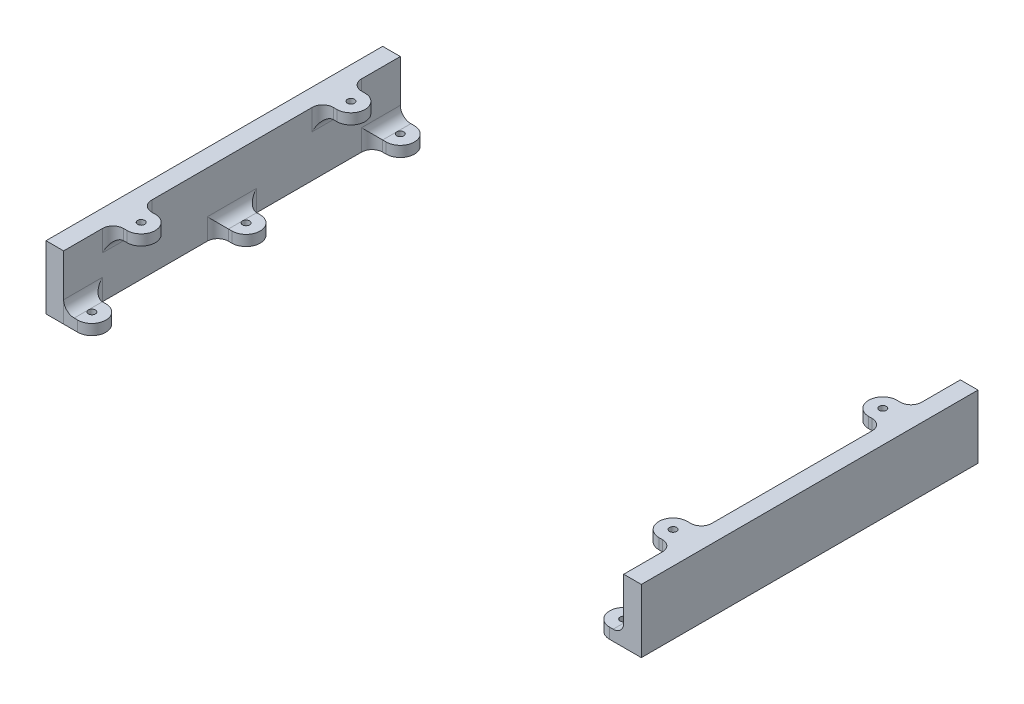
SolidWorks part; units mm, degrees
ref_plane "Front Plane" through (0, 0, 0) normal (0, 0, 1) x (1, 0, 0)
ref_plane "Top Plane" through (0, 0, 0) normal (0, 1, 0) x (1, 0, 0)
ref_plane "Right Plane" through (0, 0, 0) normal (1, 0, 0) x (0, 0, -1)
sketch "Sketch1" plane through (0, 20, 0) normal (0, 1, 0) x (1, 0, 0)
  line L11 (-48.875, 4.25) -> (-53.875, 4.25)
  line L12 (-53.875, 4.25) -> (-53.875, -91.25)
  line L13 (-53.875, -91.25) -> (-48.875, -91.25)
  line L14 (-48.875, -91.25) -> (-44.875, -91.25)
  line L15 (-44.875, -83.25) -> (-45.875, -83.25)
  line L16 (-48.875, -80.25) -> (-48.875, -50.5)
  line L17 (-45.875, -47.5) -> (-44.875, -47.5)
  line L18 (-44.875, -39.5) -> (-45.875, -39.5)
  line L19 (-48.875, -36.5) -> (-48.875, -6.75)
  line L20 (-45.875, -3.75) -> (-44.875, -3.75)
  line L21 (-44.875, 4.25) -> (-48.875, 4.25)
  line L22 (-48.875, 4.25) -> (-53.875, 4.25)
  line L23 (-53.875, 4.25) -> (-53.875, -91.25)
  line L24 (-53.875, -91.25) -> (-48.875, -91.25)
  line L25 (-48.875, -91.25) -> (-44.875, -91.25)
  line L26 (-44.875, -83.25) -> (-45.875, -83.25)
  line L27 (-48.875, -80.25) -> (-48.875, -50.5)
  line L28 (-45.875, -47.5) -> (-44.875, -47.5)
  line L29 (-44.875, -39.5) -> (-45.875, -39.5)
  line L30 (-48.875, -36.5) -> (-48.875, -6.75)
  line L31 (-45.875, -3.75) -> (-44.875, -3.75)
  line L32 (-44.875, 4.25) -> (-48.875, 4.25)
  line L33 (115, 4.25) -> (110, 4.25)
  line L34 (110, 4.25) -> (106, 4.25)
  line L35 (106, -3.75) -> (107, -3.75)
  line L36 (110, -6.75) -> (110, -36.5)
  line L37 (107, -39.5) -> (106, -39.5)
  line L38 (106, -47.5) -> (107, -47.5)
  line L39 (110, -50.5) -> (110, -80.25)
  line L40 (107, -83.25) -> (106, -83.25)
  line L41 (106, -91.25) -> (110, -91.25)
  line L42 (110, -91.25) -> (115, -91.25)
  line L43 (115, -91.25) -> (115, 4.25)
  line L44 (115, 4.25) -> (110, 4.25)
  line L45 (110, 4.25) -> (106, 4.25)
  line L46 (106, -3.75) -> (107, -3.75)
  line L47 (110, -6.75) -> (110, -36.5)
  line L48 (107, -39.5) -> (106, -39.5)
  line L49 (106, -47.5) -> (107, -47.5)
  line L50 (110, -50.5) -> (110, -80.25)
  line L51 (107, -83.25) -> (106, -83.25)
  line L52 (106, -91.25) -> (110, -91.25)
  line L53 (110, -91.25) -> (115, -91.25)
  line L54 (115, -91.25) -> (115, 4.25)
  circle A0 centre (106, -87.25) radius 1 construction
  circle A1 centre (106, -43.5) radius 1 construction
  circle A2 centre (106, -87.25) radius 1
  circle A3 centre (106, -43.5) radius 1
  circle A4 centre (-44.875, -87.25) radius 1 construction
  circle A5 centre (-44.875, -43.5) radius 1 construction
  circle A6 centre (-44.875, 0.25) radius 1 construction
  arc A7 (-44.875, -91.25) -> (-44.875, -83.25) centre (-44.875, -87.25) ccw
  arc A8 (-48.875, -80.25) -> (-45.875, -83.25) centre (-45.875, -80.25) ccw
  arc A9 (-45.875, -47.5) -> (-48.875, -50.5) centre (-45.875, -50.5) ccw
  arc A10 (-44.875, -47.5) -> (-44.875, -39.5) centre (-44.875, -43.5) ccw
  arc A11 (-48.875, -36.5) -> (-45.875, -39.5) centre (-45.875, -36.5) ccw
  arc A12 (-45.875, -3.75) -> (-48.875, -6.75) centre (-45.875, -6.75) ccw
  arc A13 (-44.875, -3.75) -> (-44.875, 4.25) centre (-44.875, 0.25) ccw
  arc A14 (-44.875, -91.25) -> (-44.875, -83.25) centre (-44.875, -87.25) ccw
  arc A15 (-48.875, -80.25) -> (-45.875, -83.25) centre (-45.875, -80.25) ccw
  arc A16 (-45.875, -47.5) -> (-48.875, -50.5) centre (-45.875, -50.5) ccw
  arc A17 (-44.875, -47.5) -> (-44.875, -39.5) centre (-44.875, -43.5) ccw
  arc A18 (-48.875, -36.5) -> (-45.875, -39.5) centre (-45.875, -36.5) ccw
  arc A19 (-45.875, -3.75) -> (-48.875, -6.75) centre (-45.875, -6.75) ccw
  arc A20 (-44.875, -3.75) -> (-44.875, 4.25) centre (-44.875, 0.25) ccw
  arc A21 (106, 4.25) -> (106, -3.75) centre (106, 0.25) ccw
  arc A22 (110, -6.75) -> (107, -3.75) centre (107, -6.75) ccw
  arc A23 (107, -39.5) -> (110, -36.5) centre (107, -36.5) ccw
  arc A24 (106, -39.5) -> (106, -47.5) centre (106, -43.5) ccw
  arc A25 (110, -50.5) -> (107, -47.5) centre (107, -50.5) ccw
  arc A26 (107, -83.25) -> (110, -80.25) centre (107, -80.25) ccw
  arc A27 (106, -83.25) -> (106, -91.25) centre (106, -87.25) ccw
  arc A28 (106, 4.25) -> (106, -3.75) centre (106, 0.25) ccw
  arc A29 (110, -6.75) -> (107, -3.75) centre (107, -6.75) ccw
  arc A30 (107, -39.5) -> (110, -36.5) centre (107, -36.5) ccw
  arc A31 (106, -39.5) -> (106, -47.5) centre (106, -43.5) ccw
  arc A32 (110, -50.5) -> (107, -47.5) centre (107, -50.5) ccw
  arc A33 (107, -83.25) -> (110, -80.25) centre (107, -80.25) ccw
  arc A34 (106, -83.25) -> (106, -91.25) centre (106, -87.25) ccw
  circle A35 centre (106, 0.25) radius 1 construction
  circle A36 centre (-44.875, -87.25) radius 1
  circle A37 centre (-44.875, -43.5) radius 1
  circle A38 centre (-44.875, 0.25) radius 1
  circle A39 centre (106, 0.25) radius 1
  dimension "D1" = 0
  dimension "D2" = 0
extrude "LEVEL 1 mating surface" add sketch "Sketch1" along normal blind 3
sketch "Sketch2" plane through (0, 23, 0) normal (0, 1, 0) x (1, 0, 0)
  line L1 (-53.875, 4.25) -> (-48.875, 4.25)
  line L2 (-53.875, 4.25) -> (-53.875, -91.25)
  line L3 (-53.875, -91.25) -> (-48.875, -91.25)
  line L4 (-48.875, 4.25) -> (-48.875, -91.25)
  line L5 (110, 4.25) -> (115, 4.25)
  line L6 (110, 4.25) -> (110, -91.25)
  line L7 (110, -91.25) -> (115, -91.25)
  line L8 (115, 4.25) -> (115, -91.25)
extrude "LEVEL 3 riser" add sketch "Sketch2" along normal blind 15
sketch "Sketch3" plane through (0, 38, 0) normal (0, 1, 0) x (1, 0, 0)
  line L2 (-48.875, -91.25) -> (-48.875, 4.25) construction
  line L4 (-48.875, -6.75) -> (-48.875, -20.75)
  line L10 (-44.875, -43.5) -> (106, -43.5) construction
  line L11 (-44.875, -77.25) -> (-45.875, -77.25)
  line L19 (-45.875, -69.25) -> (-44.875, -69.25)
  line L23 (-45.875, -17.75) -> (-44.875, -17.75)
  line L28 (-48.875, -80.25) -> (-48.875, -66.25)
  line L29 (30.5625, -3.5) -> (30.5625, -83.5) construction
  line L36 (-44.875, -9.75) -> (-45.875, -9.75)
  line L38 (106, -9.75) -> (107, -9.75)
  line L39 (110, -80.25) -> (110, -66.25)
  line L40 (107, -17.75) -> (106, -17.75)
  line L41 (107, -69.25) -> (106, -69.25)
  line L42 (106, -77.25) -> (107, -77.25)
  line L43 (110, -6.75) -> (110, -20.75)
  circle A9 centre (-44.875, -73.25) radius 1
  arc A10 (-48.875, -80.25) -> (-45.875, -77.25) centre (-45.875, -80.25) cw
  arc A11 (-44.875, -69.25) -> (-44.875, -77.25) centre (-44.875, -73.25) cw
  arc A21 (-45.875, -17.75) -> (-48.875, -20.75) centre (-45.875, -20.75) ccw
  arc A31 (-45.875, -69.25) -> (-48.875, -66.25) centre (-45.875, -66.25) cw
  circle A32 centre (106, -13.75) radius 1
  arc A40 (-44.875, -17.75) -> (-44.875, -9.75) centre (-44.875, -13.75) ccw
  arc A41 (-48.875, -6.75) -> (-45.875, -9.75) centre (-45.875, -6.75) ccw
  circle A42 centre (-44.875, -13.75) radius 1
  arc A43 (110, -6.75) -> (107, -9.75) centre (107, -6.75) cw
  arc A44 (106, -17.75) -> (106, -9.75) centre (106, -13.75) cw
  arc A45 (107, -69.25) -> (110, -66.25) centre (107, -66.25) ccw
  arc A46 (107, -17.75) -> (110, -20.75) centre (107, -20.75) cw
  arc A47 (106, -69.25) -> (106, -77.25) centre (106, -73.25) ccw
  arc A48 (110, -80.25) -> (107, -77.25) centre (107, -80.25) ccw
  circle A49 centre (106, -73.25) radius 1
  point P25 (30.5625, -43.5)
  point P26 (30.5625, -43.5)
  dimension "D1" = 2
  dimension "D2" = 4
  dimension "D3" = 3
  dimension "D4" = 80
extrude "LEVEL 3 screwholes" add sketch "Sketch3" against normal blind 3
fillet "Fillet1" radius 3 5 edges at (-48.875, 23, 1.25) (-48.875, 35, 13.75) (-48.875, 23, 43.5) (-48.875, 23, 85.75) (-48.875, 35, 73.25)
fillet "Fillet2" radius 3 5 edges at (110, 23, 85.75) (110, 23, 43.5) (110, 23, 1.25) (110, 35, 13.75) (110, 35, 73.25)
